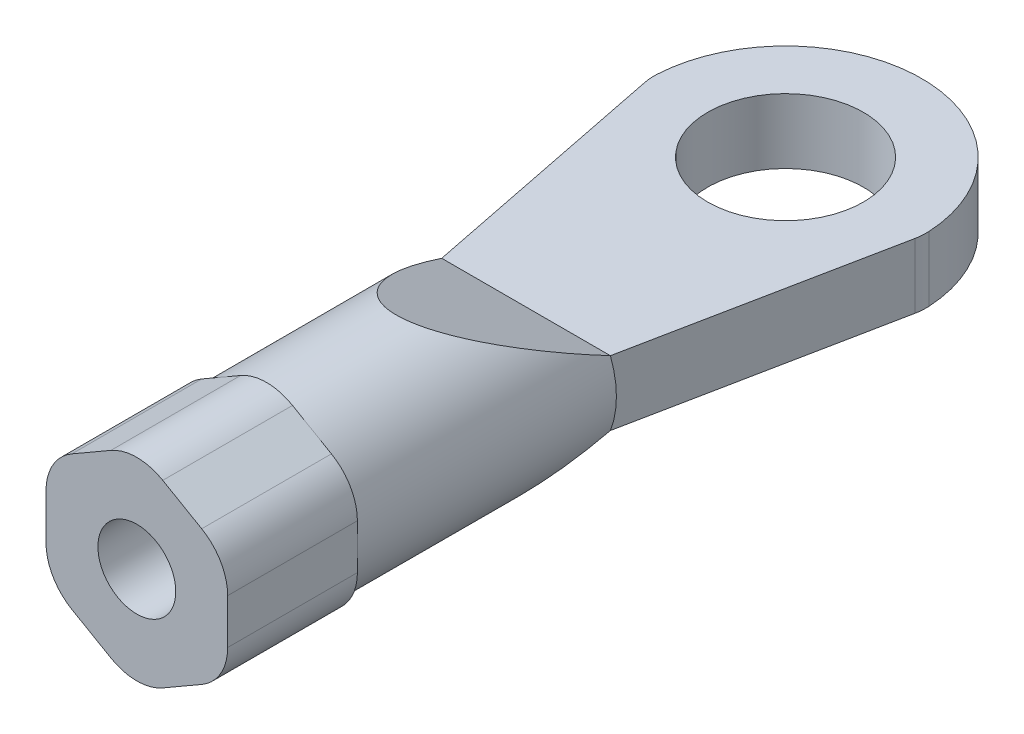
SolidWorks part; units mm, degrees
ref_plane "前视基准面" through (0, 0, 0) normal (0, 0, 1) x (1, 0, 0)
ref_plane "上视基准面" through (0, 0, 0) normal (0, 1, 0) x (1, 0, 0)
ref_plane "右视基准面" through (0, 0, 0) normal (1, 0, 0) x (0, 0, -1)
sketch "草图1" plane through (0, 0, 0) normal (0, 1, 0) x (1, 0, 0)
  line L0 (-5.25, 0) -> (-3.25, -10)
  line L1 (5.25, 0) -> (3.25, -10)
  line L2 (0, 0) -> (0, -12.7188) construction
  line L3 (-3.25, -10) -> (3.25, -10)
  circle A0 centre (0, 0) radius 5.25
  dimension "D1" = 10.5
  dimension "D2" = 6.5
  dimension "D3" = 10
extrude "凸台-拉伸1" add sketch "草图1" along normal blind 2.5 contours L1 A0 L0 | L2 A0 L0 L3 | A0 L2 L3 L1 region at (0, 0, -0.0033) region at (-2.1178, 0, 7.0378) region at (2.1178, 0, 7.0378)
sketch "草图2" plane through (0, 2.5, 0) normal (0, 1, 0) x (1, 0, 0)
  circle A0 centre (0, 0) radius 3
  dimension "D1" = 6
extrude "切除-拉伸1" cut sketch "草图2" against normal blind 2.5
fillet "圆角1" radius 2 2 edges at (-5.25, 1.25, 0) (5.25, 1.25, 0)
sketch "草图3" plane through (0, 0, 10) normal (0, 0, 1) x (1, 0, 0)
  line L0 (0, 2.5) -> (0, 0) construction
  line L1 (-3.25, 2.5) -> (3.25, 2.5) construction
  circle A0 centre (0, 1.25) radius 3.4821
extrude "凸台-拉伸2" add sketch "草图3" along normal blind 15
sketch "草图5" plane through (0, 0, 0) normal (1, 0, 0) x (0, 0, -1)
  line L0 (-10, 2.5) -> (-15, 4.7321)
  line L1 (-10, 4.7321) -> (-25, 4.7321) construction
  line L2 (-15, 4.7321) -> (-10, 4.7321)
  line L3 (-10, 4.7321) -> (-10, 2.5)
  line L4 (-10, 0) -> (-15, -2.2321)
  line L5 (-25, -2.2321) -> (-10, -2.2321) construction
  line L6 (-15, -2.2321) -> (-10, -2.2321)
  line L7 (-10, -2.2321) -> (-10, 0)
  dimension "D1" = 5
  dimension "D2" = 5
extrude "切除-拉伸2" cut sketch "草图5" against normal blind 15 and the other way blind 15
sketch "草图6" plane through (0, 0, 25) normal (0, 0, 1) x (1, 0, 0)
  circle A0 centre (0, 1.25) radius 1.5
  dimension "D1" = 3
extrude "切除-拉伸3" cut sketch "草图6" against normal blind 10
sketch "草图7" plane through (0, 0, 25) normal (0, 0, 1) x (1, 0, 0)
  line L0 (-3.5, 1.25) -> (3.5, 1.25) construction
  line L1 (0, 5.2915) -> (-3.5, 3.2707)
  line L2 (-3.5, 3.2707) -> (-3.5, -0.7707)
  line L3 (-3.5, -0.7707) -> (0, -2.7915)
  line L4 (0, -2.7915) -> (3.5, -0.7707)
  line L5 (3.5, -0.7707) -> (3.5, 3.2707)
  line L6 (3.5, 3.2707) -> (0, 5.2915)
  circle A0 centre (0, 1.25) radius 3.5 construction
  dimension "D1" = 7
extrude "凸台-拉伸3" add sketch "草图7" against normal blind 5
sketch "草图8" plane through (0, 0, 25) normal (0, 0, 1) x (1, 0, 0)
  circle A0 centre (0, 1.25) radius 1.5
  dimension "D1" = 3
extrude "切除-拉伸4" cut sketch "草图8" against normal blind 5
fillet "圆角2" radius 2 6 edges at (0, -2.7915, 22.5) (3.5, -0.7707, 22.5) (-3.5, -0.7707, 22.5) (-3.5, 3.2707, 22.5) (0, 5.2915, 22.5) (3.5, 3.2707, 22.5)
sketch "草图9" plane through (0, 0, 0) normal (1, 0, 0) x (0, 0, -1)
  point P0 (0, 1.25)
